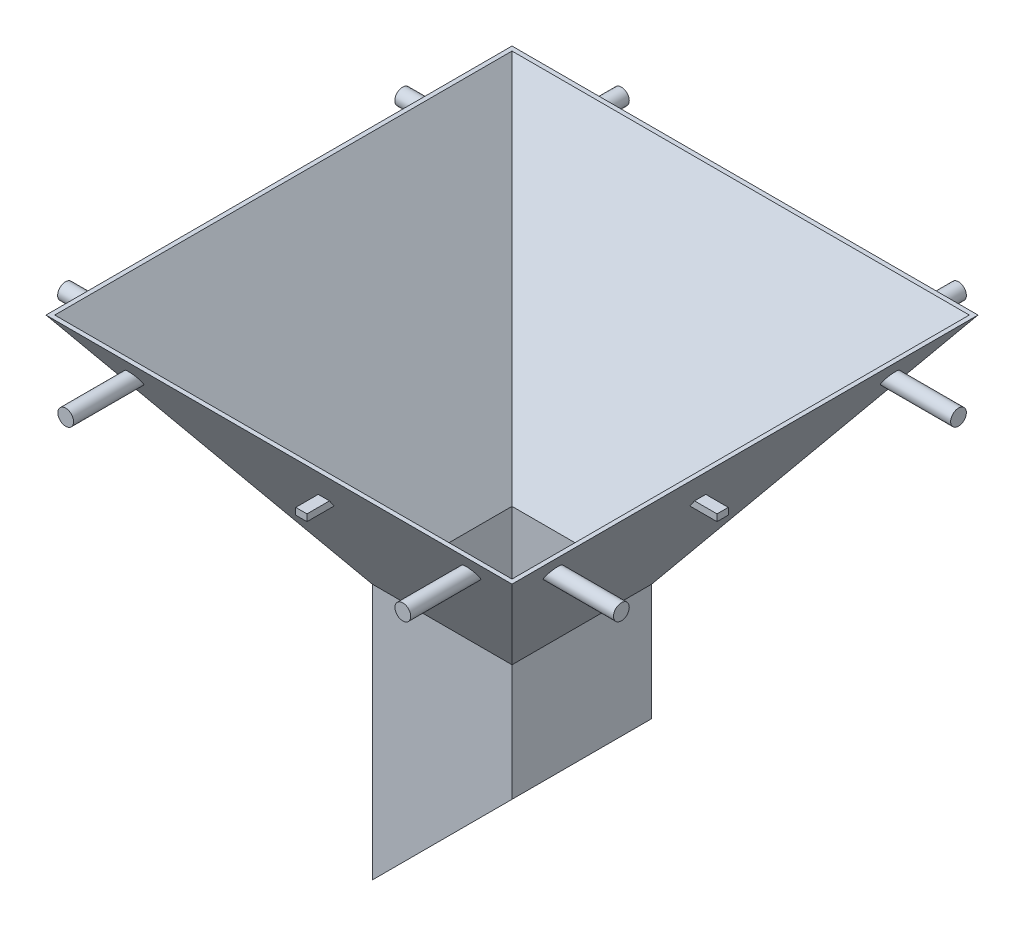
SolidWorks part; units mm, degrees
ref_plane "Alzado" through (0, 0, 0) normal (0, 0, 1) x (1, 0, 0)
ref_plane "Planta" through (0, 0, 0) normal (0, 1, 0) x (1, 0, 0)
ref_plane "Vista lateral" through (0, 0, 0) normal (1, 0, 0) x (0, 0, -1)
sketch "Croquis2" plane through (0, 0, 0) normal (0, 1, 0) x (1, 0, 0)
  line L1 (0, 0) -> (414.7, 0)
  line L2 (0, 0) -> (0, 414.7)
  line L3 (0, 414.7) -> (414.7, 414.7)
  line L4 (414.7, 0) -> (414.7, 414.7)
  dimension "D1" = 414.7
ref_plane "Plano1" through (0, -207.4, 0) normal (0, 1, 0) x (1, 0, 0)
sketch "Croquis3" plane through (0, -207.4, 0) normal (0, 1, 0) x (1, 0, 0)
  line L0 (207.35, 414.7) -> (207.35, 0) construction
  line L1 (0, 414.7) -> (414.7, 414.7) construction
  line L2 (0, 0) -> (414.7, 0) construction
  line L3 (207.35, 0) -> (414.7, 207.35) construction
  line L4 (414.7, 0) -> (414.7, 414.7) construction
  line L5 (414.7, 207.35) -> (0, 207.35) construction
  line L6 (0, 0) -> (0, 414.7) construction
  line L8 (145.2, 269.5) -> (269.5, 269.5)
  line L9 (145.2, 269.5) -> (145.2, 145.2)
  line L10 (145.2, 145.2) -> (269.5, 145.2)
  line L11 (269.5, 269.5) -> (269.5, 145.2)
  line L12 (145.2, 269.5) -> (269.5, 145.2) construction
  line L13 (145.2, 145.2) -> (269.5, 269.5) construction
  point P12 (207.35, 207.35)
  dimension "D2" = 124.3
loft "Recubrir1" add profiles "Croquis2", "Croquis3"
sketch "Croquis4" plane through (0, -207.4, 0) normal (0, -1, 0) x (1, 0, 0)
  line L1 (145.2, -145.2) -> (269.5, -145.2)
  line L2 (145.2, -145.2) -> (145.2, -269.5)
  line L3 (145.2, -269.5) -> (269.5, -269.5)
  line L4 (269.5, -145.2) -> (269.5, -269.5)
  line L5 (145.2, -145.2) -> (269.5, -269.5) construction
  line L6 (145.2, -269.5) -> (269.5, -145.2) construction
  point P0 (207.35, -207.35)
extrude "Saliente-Extruir1" add sketch "Croquis4" along normal blind 103.7
sketch "Croquis5" plane through (0, 0, -145.2) normal (0, 0, 1) x (1, 0, 0)
  line L0 (145.2, -311.1) -> (145.2, -435.4)
  line L1 (145.2, -435.4) -> (269.5, -311.1)
  line L2 (269.5, -311.1) -> (145.2, -311.1) construction
  line L3 (145.2, -311.1) -> (269.5, -311.1)
  dimension "D1" = 124.3
  dimension "D2" = 45
extrude "Saliente-Extruir2" add sketch "Croquis5" against normal up to surface (124.3 mm away) up to face at (222.8875, -285.175, -269.5)
shell "Vaciado1" thickness 3.175 removed face at (207.35, 0, -207.35)
ref_plane "Plano2" through (0, 0, 0) normal (1, 0, 0) x (0, 0, -1)
sketch "Croquis6" plane through (0, 0, 0) normal (1, 0, 0) x (0, 0, -1)
  line L0 (250, -50) -> (250, -100) construction
  line L1 (414.7, 0) -> (0, 0) construction
  line L2 (414.7, 0) -> (414.7, 10.241) construction
  line L3 (550, -50) -> (-50, -50) construction
  line L4 (-50, -100) -> (550, -100) construction
  line L5 (250, -100) -> (357.35, -100) construction
  line L6 (357.35, -100) -> (357.35, -50) construction
  line L7 (414.7, 10.241) -> (0, 10.241) construction
  line L8 (0, 10.241) -> (0, 0) construction
  line L9 (207.35, 10.241) -> (207.35, -30) construction
  circle A0 centre (357.35, -30) radius 7
  circle A2 centre (57.35, -30) radius 7
  dimension "D1" = 14
  dimension "D2" = 30
  dimension "D3" = 150
extrude "Saliente-Extruir3" add sketch "Croquis6" along normal up to surface and the other way blind 40 up to face at (36.3, -51.85, -274.725)
ref_plane "Plano3" through (0, 0, 0) normal (0, 0, 1) x (1, 0, 0)
sketch "Croquis7" plane through (0, 0, 0) normal (0, 0, 1) x (1, 0, 0)
  line L0 (0, 0) -> (0, 19.7266) construction
  line L1 (0, -228.085) -> (0, 228.085) construction
  line L2 (0, 19.7266) -> (415.0782, 19.7266) construction
  line L3 (415.0782, 19.7266) -> (414.7, 0) construction
  line L4 (207.5391, 19.7266) -> (207.5391, -72.7788) construction
  line L5 (0, 0) -> (414.7, 0) construction
  circle A0 centre (57.5391, -30) radius 7
  circle A1 centre (357.5391, -30) radius 7
  dimension "D1" = 14
  dimension "D2" = 30
  dimension "D3" = 150
extrude "Saliente-Extruir4" add sketch "Croquis7" along normal blind 40 and the other way up to surface other way up to face at (139.975, -51.85, -36.3)
ref_plane "Plano4" through (414.7, 0, 0) normal (1, 0, 0) x (0, 0, -1)
sketch "Croquis8" plane through (414.7, 0, 0) normal (1, 0, 0) x (0, 0, -1)
  line L0 (0, 0) -> (0, 56.09) construction
  line L1 (0, 56.09) -> (414.7, 56.09) construction
  line L2 (414.7, 56.09) -> (414.7, 0) construction
  line L3 (207.35, 56.09) -> (207.35, -57.8935) construction
  line L4 (0, 0) -> (414.7, 0) construction
  circle A0 centre (57.35, -30) radius 7
  circle A1 centre (357.35, -30) radius 7
  dimension "D1" = 14
  dimension "D2" = 30
  dimension "D3" = 150
extrude "Saliente-Extruir5" add sketch "Croquis8" along normal blind 40 and the other way up to surface other way up to face at (378.4, -51.85, -139.975)
ref_plane "Plano5" through (0, 0, -414.7) normal (0, 0, -1) x (-1, 0, 0)
sketch "Croquis9" plane through (0, 0, -414.7) normal (0, 0, -1) x (-1, 0, 0)
  line L0 (-414.7, 0) -> (-414.7, 56.09) construction
  line L1 (-414.7, 56.09) -> (0, 56.09) construction
  line L2 (0, 56.09) -> (0, 0) construction
  line L3 (-414.7, 0) -> (0, 0) construction
  line L4 (-207.35, 56.09) -> (-207.35, -89.7765) construction
  circle A0 centre (-357.35, -30) radius 7
  circle A1 centre (-57.35, -30) radius 7
  dimension "D1" = 14
  dimension "D2" = 30
  dimension "D3" = 150
extrude "Saliente-Extruir6" add sketch "Croquis9" along normal blind 40 and the other way up to surface other way up to face at (274.725, -51.85, -378.4)
sketch "Croquis10" plane through (0, -207.4, 0) normal (0, 1, 0) x (1, 0, 0)
  line L0 (266.325, 266.325) -> (148.375, 266.325) construction
  line L1 (148.375, 148.375) -> (266.325, 148.375)
  line L2 (148.375, 148.375) -> (148.375, 266.325)
  line L3 (148.375, 266.325) -> (266.325, 266.325)
  line L4 (266.325, 148.375) -> (266.325, 266.325)
  line L5 (266.325, 266.325) -> (148.375, 266.325) construction
extrude "Cortar-Extruir1" cut sketch "Croquis10" against normal blind 306
ref_plane "Plano7" through (207.35, 0, 0) normal (-1, 0, 0) x (0, 0, 1)
sketch "Croquis13" plane through (207.35, 0, 0) normal (-1, 0, 0) x (0, 0, 1)
  line L0 (0, 0) -> (0, -57) construction
  line L1 (0, -57) -> (0, -207.4) construction
  line L2 (0, -207.4) -> (-145.2, -207.4) construction
  line L3 (-145.2, -207.4) -> (0, 0) construction
  line L4 (-39.9055, -57) -> (-19.9055, -57)
  line L5 (-19.9055, -57) -> (-19.9055, -63)
  line L6 (-19.9055, -63) -> (-44.1061, -63)
  line L7 (-44.1061, -63) -> (-39.9055, -57)
  line L8 (-207.35, 0) -> (-207.35, -207.4) construction
  line L9 (-414.7, 0) -> (0, 0) construction
  line L10 (-269.5, -207.4) -> (-145.2, -207.4) construction
  line L11 (-370.5939, -63) -> (-374.7945, -57)
  line L12 (-394.7945, -63) -> (-370.5939, -63)
  line L13 (-394.7945, -57) -> (-394.7945, -63)
  line L14 (-374.7945, -57) -> (-394.7945, -57)
  dimension "D1" = 150.4
  dimension "D2" = 20
  dimension "D3" = 6
extrude "Saliente-Extruir7" add sketch "Croquis13" along normal mid plane 10
ref_plane "Plano8" through (0, 0, -207.35) normal (0, 0, 1) x (1, 0, 0)
sketch "Croquis14" plane through (0, 0, -207.35) normal (0, 0, 1) x (1, 0, 0)
  line L0 (0, 0) -> (0, -57) construction
  line L1 (0, -57) -> (0, -207.4) construction
  line L2 (0, -207.4) -> (145.2, -207.4) construction
  line L3 (0, 0) -> (145.2, -207.4) construction
  line L4 (39.9055, -57) -> (19.9055, -57)
  line L5 (19.9055, -57) -> (19.9055, -63)
  line L6 (19.9055, -63) -> (44.1061, -63)
  line L7 (44.1061, -63) -> (39.9055, -57)
  line L8 (207.35, 0) -> (207.35, -207.4) construction
  line L9 (0, 0) -> (414.7, 0) construction
  line L10 (145.2, -207.4) -> (269.5, -207.4) construction
  line L11 (370.5939, -63) -> (374.7945, -57)
  line L12 (394.7945, -63) -> (370.5939, -63)
  line L13 (394.7945, -57) -> (394.7945, -63)
  line L14 (374.7945, -57) -> (394.7945, -57)
  dimension "D1" = 150.4
  dimension "D2" = 20
  dimension "D3" = 6
extrude "Saliente-Extruir8" add sketch "Croquis14" along normal mid plane 10
